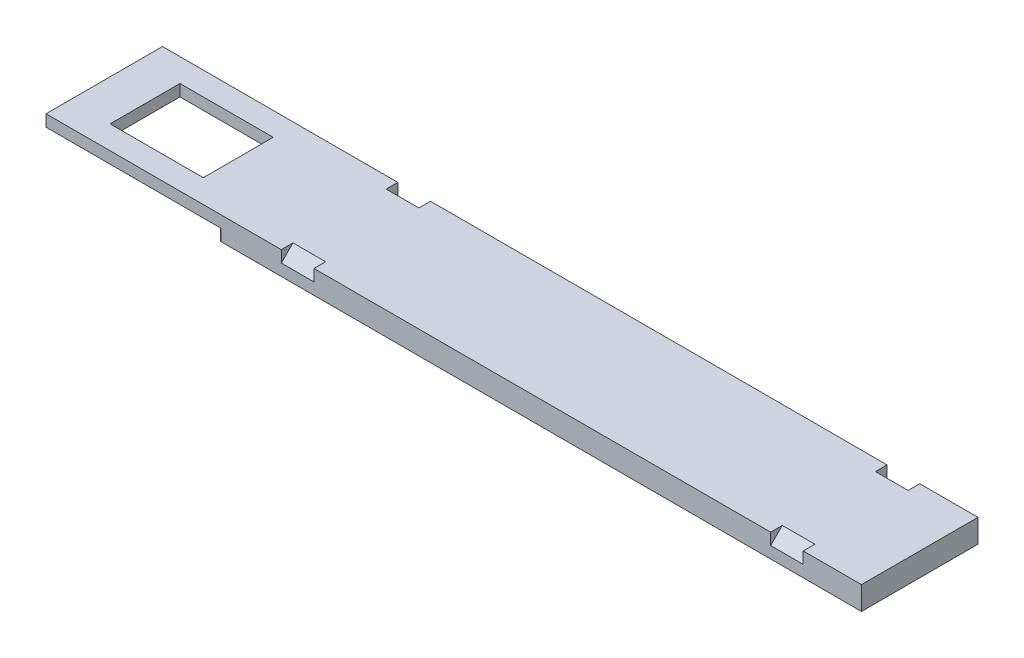
SolidWorks part; units mm, degrees
ref_plane "Front Plane" through (0, 0, 0) normal (0, 0, 1) x (1, 0, 0)
ref_plane "Top Plane" through (0, 0, 0) normal (0, 1, 0) x (1, 0, 0)
ref_plane "Right Plane" through (0, 0, 0) normal (1, 0, 0) x (0, 0, -1)
sketch "Sketch1" plane through (0, 0, 0) normal (0, 1, 0) x (1, 0, 0)
  line L1 (-35, -5) -> (35, -5)
  line L2 (-35, -5) -> (-35, 5)
  line L3 (-35, 5) -> (35, 5)
  line L4 (35, -5) -> (35, 5)
  line L5 (-35, -5) -> (35, 5) construction
  line L6 (-35, 5) -> (35, -5) construction
  point P0 (0, 0)
  dimension "D1" = 10
  dimension "D2" = 70
extrude "Boss-Extrude1" add sketch "Sketch1" along normal blind 2
sketch "Sketch2" plane through (35, 0, 0) normal (1, 0, 0) x (0, 0, -1)
  line L0 (-5, 2) -> (-5, 1)
  line L1 (-5, 2) -> (-5, 0) construction
  line L2 (-5, 2) -> (5, 2) construction
  line L3 (-5, 2) -> (-4, 2)
  line L4 (-4, 2) -> (-5, 1)
  line L5 (5, 2) -> (5, 1)
  line L6 (5, 2) -> (5, 0) construction
  line L7 (5, 1) -> (4, 2)
  line L8 (4, 2) -> (5, 2)
  dimension "D1" = 1
  dimension "D2" = 1
extrude "Cut-Extrude1" cut sketch "Sketch2" against normal blind 2.8 from offset 5 offset against normal yes
extrude "Cut-Extrude2" cut sketch "Sketch2<2>" against normal blind 2.8 from offset 47 offset against normal yes
sketch "Sketch2<2>" plane through (35, 0, 0) normal (1, 0, 0) x (0, 0, -1) same geometry as "Sketch2"
sketch "Sketch3" plane through (0, 0, 0) normal (0, -1, 0) x (1, 0, 0)
  line L0 (35, -5) -> (-35, -5) construction
  line L1 (-35, 5) -> (-20, 5)
  line L2 (-35, 5) -> (-35, -5)
  line L3 (-35, -5) -> (-20, -5)
  line L4 (-20, 5) -> (-20, -5)
  dimension "D1" = 15
extrude "Cut-Extrude3" cut sketch "Sketch3" against normal blind 1
sketch "Sketch4" plane through (0, 1, 0) normal (0, -1, 0) x (1, 0, 0)
  line L0 (-35, 5) -> (-20, -5) construction
  line L1 (-31.5, 3) -> (-23.5, 3)
  line L2 (-31.5, 3) -> (-31.5, -3)
  line L3 (-31.5, -3) -> (-23.5, -3)
  line L4 (-23.5, 3) -> (-23.5, -3)
  line L5 (-31.5, 3) -> (-23.5, -3) construction
  line L6 (-31.5, -3) -> (-23.5, 3) construction
  line L7 (-20, 5) -> (-35, -5) construction
  point P0 (-27.5, 0)
  point P13 (-22.6601, 0.715)
  point P14 (-27.5, 0)
  dimension "D1" = 8
  dimension "D2" = 6
extrude "Cut-Extrude4" cut sketch "Sketch4" against normal through all
